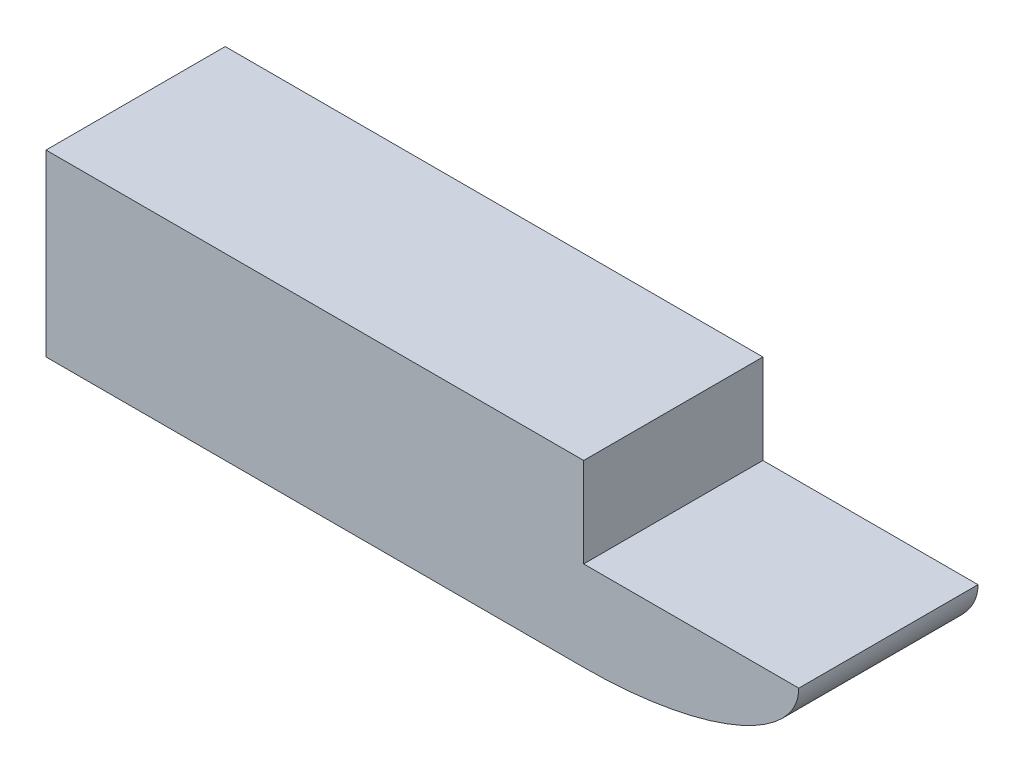
SolidWorks part; units mm, degrees
ref_plane "Front Plane" through (0, 0, 0) normal (0, 0, 1) x (1, 0, 0)
ref_plane "Top Plane" through (0, 0, 0) normal (0, 1, 0) x (1, 0, 0)
ref_plane "Right Plane" through (0, 0, 0) normal (1, 0, 0) x (0, 0, -1)
sketch "Sketch1" plane through (0, 0, 0) normal (0, 0, 1) x (1, 0, 0)
  line L1 (-457.2, -152.4) -> (457.2, -152.4)
  line L2 (-457.2, -152.4) -> (-457.2, 152.4)
  line L3 (-457.2, 152.4) -> (457.2, 152.4)
  line L4 (457.2, -152.4) -> (457.2, 152.4)
  line L5 (-457.2, -152.4) -> (457.2, 152.4) construction
  line L6 (-457.2, 152.4) -> (457.2, -152.4) construction
  point P0 (0, 0)
extrude "Boss-Extrude1" add sketch "Sketch1" along normal mid plane 304.8
sketch "Sketch2" plane through (0, 0, 152.4) normal (0, 0, 1) x (1, 0, 0)
  line L0 (457.2, -152.4) -> (457.2, 152.4) construction
  line L1 (457.2, 0) -> (823.0024, 0)
  line L2 (457.2, 0) -> (457.2, -152.4)
  ellipse E0 centre (457.2, 0) end of major axis (91.3976, 0) minor radius 152.4
  line M1 (457.2, -152.4) -> (457.2, 152.4)
extrude "Boss-Extrude2" add sketch "Sketch2" against normal blind 304.8 contours E0 L1 M1 region at (612.4513, -64.6806, 152.4)
